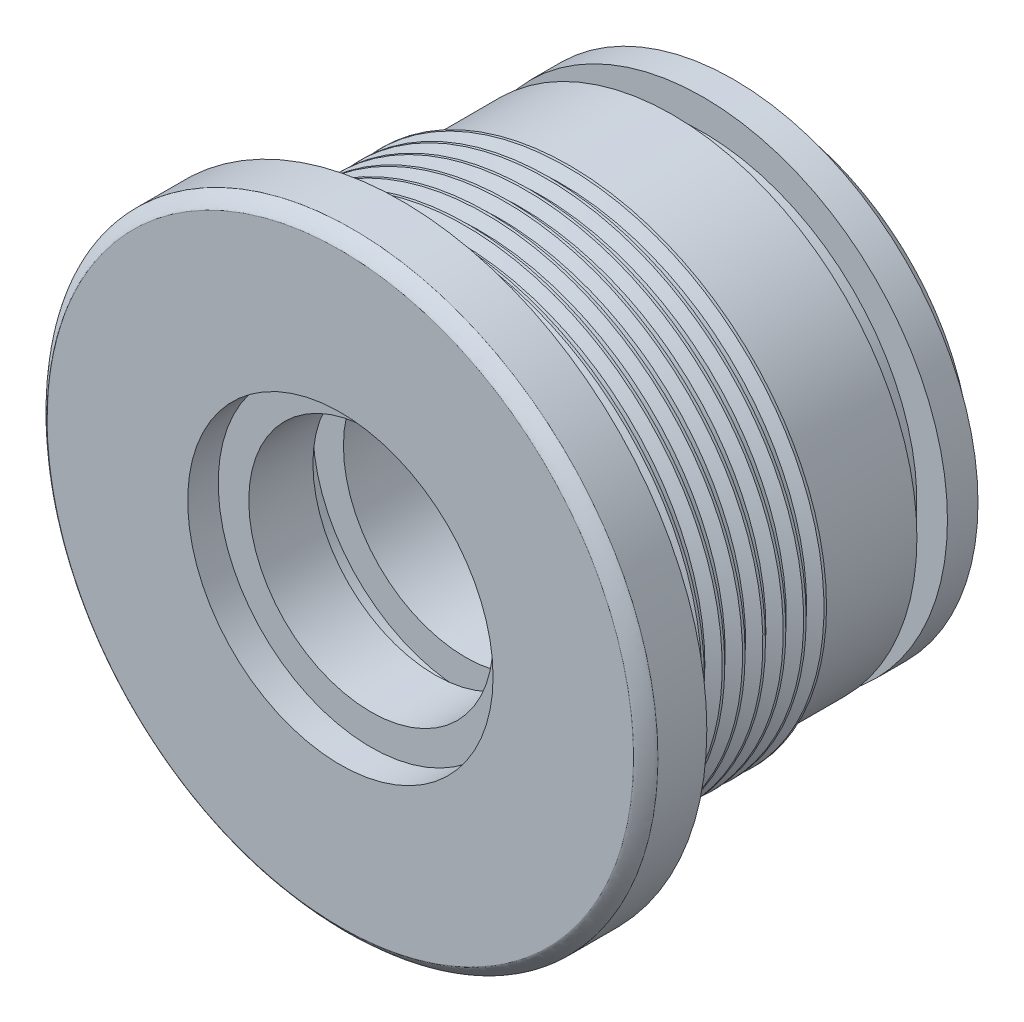
SolidWorks part; units mm, degrees
ref_plane "Front" through (0, 0, 0) normal (0, 0, 1) x (1, 0, 0)
ref_plane "Top" through (0, 0, 0) normal (0, 1, 0) x (1, 0, 0)
ref_plane "Right" through (0, 0, 0) normal (1, 0, 0) x (0, 0, -1)
sketch "Sketch1" plane through (0, 0, 0) normal (0, 0, 1) x (1, 0, 0)
  circle A0 centre (0, 0) radius 31.75
  circle A1 centre (0, 0) radius 12.7
  dimension "D1" = 63.5
  dimension "D2" = 25.4
extrude "Boss-Extrude1" add sketch "Sketch1" along normal blind 44.069
sketch "Sketch2" plane through (0, 0, 44.069) normal (0, 0, 1) x (1, 0, 0)
  circle A0 centre (0, 0) radius 31.75
  circle A1 centre (0, 0) radius 25.4
  circle A2 centre (0, 0) radius 31.75 construction
  dimension "D1" = 6.35
extrude "Cut-Extrude1" cut sketch "Sketch2" against normal through all from offset 6.35 offset against normal yes
fillet "Fillet1" radius 1.27 1 edges at (31.75, 0, 44.069) conic rho 0.1
sketch "Sketch3" plane through (0, 0, 44.069) normal (0, 0, 1) x (1, 0, 0)
  circle A0 centre (0, 0) radius 15.875
  circle A1 centre (0, 0) radius 12.7 construction
  dimension "D1" = 3.175
extrude "Cut-Extrude2" cut sketch "Sketch3" against normal blind 3.175
extrude "Cut-Extrude3" cut sketch "Sketch3<2>" against normal blind 3.175 from offset 9.8425 offset against normal yes
sketch "Sketch3<2>" plane through (0, 0, 44.069) normal (0, 0, 1) x (1, 0, 0) same geometry as "Sketch3"
thread "Thread1" pitch 2.1167 method extrude profile "Thread Profile1" start angle 0, offset 1.27, length 19.05, pitch 2.1167, diameter 50.8
ref_plane "Plane1" through (-25.4, 0, 38.989) normal (0, -1, 0) x (-1, 0, 0)
sketch "Thread Profile1" plane through (-25.4, 0, 38.989) normal (0, -1, 0) x (-1, 0, 0)
  line L0 (0, 0) -> (0, 2.1167) construction
  line L1 (0, 0) -> (1.1457, 0.6615)
  line L2 (1.1457, 0.6615) -> (1.1457, 0.926)
  line L3 (1.1457, 0.926) -> (0, 1.5875)
  line L4 (1.1457, 0.7937) -> (0, 0.7937) construction
  line L11 (0, 0) -> (0, 1.5875)
  point P2 (0, 0)
  dimension "Pitch" = 2.1167
  dimension "Profile_Angle" = 60
  dimension "Profile_Land" = 0.2646
  dimension "Profile_Height" = 1.1457
sketch "Sketch8" plane through (0, 0, 0) normal (0, 0, -1) x (-1, 0, 0)
  circle A0 centre (0, 0) radius 25.4
  circle A1 centre (0, 0) radius 22.225
  circle A2 centre (0, 0) radius 25.4 construction
  dimension "D1" = 3.175
extrude "Cut-Extrude4" cut sketch "Sketch8" against normal blind 3.175
extrude "Cut-Extrude5" cut sketch "Sketch8<2>" against normal blind 3.175 from offset 6.35 offset against normal yes
sketch "Sketch8<2>" plane through (0, 0, 0) normal (0, 0, -1) x (-1, 0, 0) same geometry as "Sketch8"
fillet "Fillet2" radius 1.27 1 edges at (-22.225, 0, 0)
